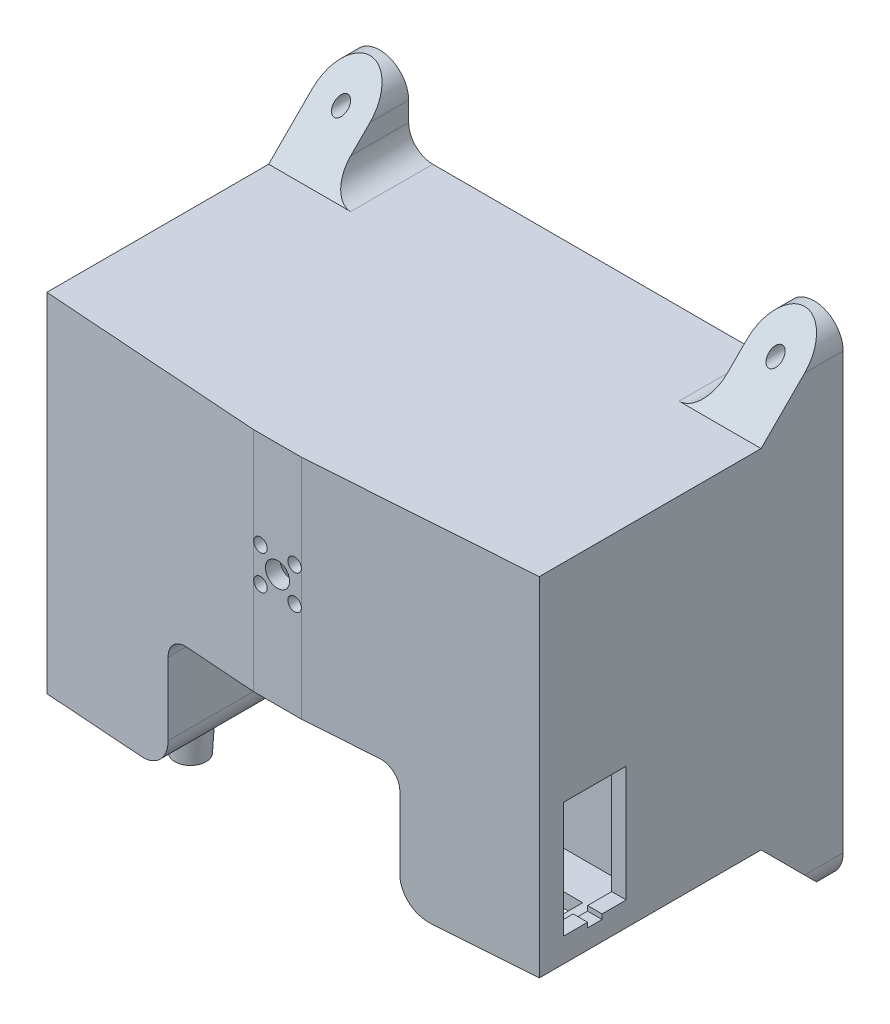
SolidWorks part; units mm, degrees
material "ABS"
ref_plane "Спереди" through (0, 0, 0) normal (0, 0, 1) x (1, 0, 0)
ref_plane "Сверху" through (0, 0, 0) normal (0, 1, 0) x (1, 0, 0)
ref_plane "Справа" through (0, 0, 0) normal (1, 0, 0) x (0, 0, -1)
sketch "Model" plane through (0, 0, 0) normal (0, 0, 1) x (1, 0, 0)
  line L0 (-25, 35) -> (-25, 20)
  line L1 (-70, 40) -> (-30, 40)
  line L2 (-75, 20) -> (-75, 35)
  line L3 (1, 49) -> (1, 95)
  line L5 (0, 95) -> (0, 78.8869)
  line L6 (-10, 85) -> (-10, 95)
  line L7 (-90, 85) -> (-10, 85)
  line L8 (-90, 95) -> (-90, 85)
  line L9 (-100, 78.8869) -> (-100, 95)
  line L10 (-100, 78.8869) -> (-100, 76.8869)
  line L11 (0, 76.8869) -> (0, 65)
  line L12 (-100, 65) -> (-100, 63)
  line L13 (-100, 65) -> (-100, 76.8869)
  line L14 (-90, 15) -> (-90, 5)
  line L15 (-80, 15) -> (-90, 15)
  line L16 (-75, 35) -> (-75, 20)
  line L17 (-30, 40) -> (-70, 40)
  line L18 (-25, 20) -> (-25, 35)
  line L19 (-10, 15) -> (-20, 15)
  line L20 (-10, 5) -> (-10, 15)
  line L21 (0, 28) -> (0, 5)
  line L22 (-10, 28) -> (0, 28)
  line L23 (-12, 48) -> (-12, 30)
  line L24 (0, 50) -> (-10, 50)
  line L25 (0, 63) -> (0, 50)
  line L26 (0, 78.8869) -> (0, 76.8869)
  line L27 (-100, 5) -> (-100, 63)
  line L28 (-101, 95) -> (-101, 5)
  line L29 (-89, 86) -> (-89, 95)
  line L30 (-11, 86) -> (-89, 86)
  line L31 (-11, 95) -> (-11, 86)
  line L32 (-10, 49) -> (1, 49)
  line L33 (-11, 30) -> (-11, 48)
  line L34 (1, 29) -> (-10, 29)
  line L35 (1, 5) -> (1, 29)
  line L36 (-11, 14) -> (-11, 5)
  line L37 (-20, 14) -> (-11, 14)
  line L38 (-26, 35) -> (-26, 20)
  line L39 (-70, 39) -> (-30, 39)
  line L40 (-74, 20) -> (-74, 35)
  line L41 (0, 65) -> (0, 63)
  line L42 (-89, 5) -> (-89, 14)
  line L52 (-80, 14) -> (-89, 14)
  arc A0 (-25, 35) -> (-30, 40) centre (-30, 35) ccw
  arc A1 (-70, 40) -> (-75, 35) centre (-70, 35) ccw
  circle A2 centre (-95, 95) radius 1.4
  circle A3 centre (-95, 95) radius 2.4
  circle A4 centre (-5, 95) radius 1.4
  circle A5 centre (-5, 95) radius 2.4
  circle A6 centre (-95, 5) radius 1.4
  circle A7 centre (-95, 5) radius 2.4
  circle A8 centre (-5, 5) radius 2.4
  circle A9 centre (-5, 5) radius 1.4
  arc A10 (0, 95) -> (-10, 95) centre (-5, 95) ccw
  arc A11 (-90, 95) -> (-100, 95) centre (-95, 95) ccw
  arc A12 (-100, 5) -> (-90, 5) centre (-95, 5) ccw
  arc A13 (-80, 15) -> (-75, 20) centre (-80, 20) ccw
  arc A14 (-70, 40) -> (-75, 35) centre (-70, 35) ccw
  arc A15 (-25, 35) -> (-30, 40) centre (-30, 35) ccw
  arc A16 (-25, 20) -> (-20, 15) centre (-20, 20) ccw
  arc A17 (-10, 5) -> (0, 5) centre (-5, 5) ccw
  arc A18 (-12, 30) -> (-10, 28) centre (-10, 30) ccw
  arc A19 (-10, 50) -> (-12, 48) centre (-10, 48) ccw
  arc A20 (-89, 95) -> (-101, 95) centre (-95, 95) ccw
  arc A21 (1, 95) -> (-11, 95) centre (-5, 95) ccw
  arc A22 (-10, 49) -> (-11, 48) centre (-10, 48) ccw
  arc A23 (-11, 30) -> (-10, 29) centre (-10, 30) ccw
  arc A24 (-11, 5) -> (1, 5) centre (-5, 5) ccw
  arc A25 (-26, 20) -> (-20, 14) centre (-20, 20) ccw
  arc A26 (-26, 35) -> (-30, 39) centre (-30, 35) ccw
  arc A27 (-70, 39) -> (-74, 35) centre (-70, 35) ccw
  arc A28 (-80, 14) -> (-74, 20) centre (-80, 20) ccw
  arc A29 (-101, 5) -> (-89, 5) centre (-95, 5) ccw
extrude "Бобышка-Вытянуть1" add sketch "Model" along normal blind 60 contours L28 A29 L42 L52 A28 L40 A27 L39 A26 L38 A25 L37 L36 A24 L35 L34 A23 L33 A22 L32 L3 A21 L31 L30 L29 A20 L24 A19 L23 A18 L22 L21 A17 L20 L19 A16 L0 A0 L1 A1 L2 A13 L15 L14 A12 L27 L12 L13 L10 L9 region at (-4.5, 49.1442, 0)
sketch "Эскиз2" plane through (0, 0, 60) normal (0, 0, 1) x (1, 0, 0)
  line L0 (-90, 85) -> (-100, 85)
  line L1 (-100, 5) -> (-100, 95) construction
  line L2 (-100, 85) -> (-100, 95)
  line L3 (-90, 95) -> (-90, 85)
  line L4 (-10, 95) -> (-10, 85)
  line L5 (-10, 85) -> (0, 85)
  line L6 (0, 95) -> (0, 50) construction
  line L7 (0, 85) -> (0, 95)
  line L8 (-10, 5) -> (-10, 15)
  line L9 (-10, 15) -> (0, 15)
  line L10 (0, 28) -> (0, 5) construction
  line L11 (0, 15) -> (0, 5)
  line L12 (-90, 5) -> (-90, 15)
  line L13 (-90, 15) -> (-100, 15)
  line L14 (-100, 15) -> (-100, 5)
  arc A0 (-90, 95) -> (-100, 95) centre (-95, 95) ccw construction
  arc A1 (-90, 95) -> (-100, 95) centre (-95, 95) ccw
  arc A2 (0, 95) -> (-10, 95) centre (-5, 95) ccw construction
  arc A3 (0, 95) -> (-10, 95) centre (-5, 95) ccw
  arc A4 (-10, 5) -> (0, 5) centre (-5, 5) ccw construction
  arc A5 (-10, 5) -> (0, 5) centre (-5, 5) ccw
  arc A6 (-100, 5) -> (-90, 5) centre (-95, 5) ccw construction
  arc A7 (-100, 5) -> (-90, 5) centre (-95, 5) ccw
extrude "Бобышка-Вытянуть2" add sketch "Эскиз2" against normal up to surface (60 mm away) up to face at (-40.1857, 40.5385, 0)
ref_plane "Плоскость1" through (0, 62.5, 0) normal (0, 1, 0) x (1, 0, 0)
sketch "Эскиз4" plane through (0, 62.5, 0) normal (0, 1, 0) x (1, 0, 0)
  line L0 (-100, -60) -> (-55, -63.1467)
  line L1 (-55, -63.1467) -> (-45, -63.1467)
  line L2 (-50, 0) -> (-50, -60) construction
  line L3 (-70, 0) -> (-30, 0) construction
  line L4 (-70, -60) -> (-30, -60) construction
  line L5 (-50, -60) -> (-50, -63.1467) construction
  line L6 (-100, -60) -> (-101, -60)
  line L7 (-101, -60) -> (-101, -62.9374)
  line L8 (-101, -62.9374) -> (-55, -66.154)
  line L9 (-55, -66.154) -> (-45, -66.154)
  line L10 (-55, -63.1467) -> (-55, -66.154) construction
  line L11 (1, -62.9374) -> (-45, -66.154)
  line L12 (0, -60) -> (-45, -63.1467)
  line L13 (1, -60) -> (1, -62.9374)
  line L14 (0, -60) -> (1, -60)
  point P16 (-50, -66.154)
  dimension "D1" = 4
  dimension "D2" = 5
  dimension "D3" = 3
extrude "Бобышка-Вытянуть3" add sketch "Эскиз4" along normal up to surface (22.5 mm away) up to face at (-50, 85, 30)
extrude "Бобышка-Вытянуть4" add sketch "Эскиз4<2>" against normal up to surface (48.5 mm away) up to face at (-15.5, 14, 30)
sketch "Эскиз4<2>" plane through (0, 62.5, 0) normal (0, 1, 0) x (1, 0, 0) same geometry as "Эскиз4"
sketch "Эскиз5" plane through (0, 0, 0) normal (0, 0, -1) x (-1, 0, 0)
  line L0 (-1, 29) -> (10, 29) construction
  line L1 (11, 30) -> (11, 48) construction
  line L2 (10, 49) -> (-1, 49) construction
  line L3 (74, 20) -> (74, 35) construction
  line L4 (70, 39) -> (30, 39) construction
  line L5 (26, 35) -> (26, 20) construction
  line L6 (-1, 29) -> (10, 29)
  line L7 (11, 30) -> (11, 48)
  line L8 (10, 49) -> (-1, 49)
  line L9 (74, 20) -> (74, 35)
  line L10 (70, 39) -> (30, 39)
  line L11 (26, 35) -> (26, 20)
  line L12 (-1, 49) -> (-1, 29)
  line L13 (20, 14) -> (80, 14)
  arc A0 (10, 29) -> (11, 30) centre (10, 30) ccw construction
  arc A1 (11, 48) -> (10, 49) centre (10, 48) ccw construction
  arc A2 (74, 20) -> (80, 14) centre (80, 20) ccw construction
  arc A3 (74, 35) -> (70, 39) centre (70, 35) ccw construction
  arc A4 (30, 39) -> (26, 35) centre (30, 35) ccw construction
  arc A5 (20, 14) -> (26, 20) centre (20, 20) ccw construction
  arc A6 (10, 29) -> (11, 30) centre (10, 30) ccw
  arc A7 (11, 48) -> (10, 49) centre (10, 48) ccw
  arc A8 (74, 20) -> (80, 14) centre (80, 20) ccw
  arc A9 (74, 35) -> (70, 39) centre (70, 35) ccw
  arc A10 (30, 39) -> (26, 35) centre (30, 35) ccw
  arc A11 (20, 14) -> (26, 20) centre (20, 20) ccw
extrude "Вырез-Вытянуть1" cut sketch "Эскиз5" against normal through all
sketch "Эскиз6" plane through (0, 0, 60) normal (0, 0, 1) x (1, 0, 0)
  line L8 (0, 49) -> (0, 50)
  line L9 (0, 50) -> (-10, 50)
  line L10 (-12, 48) -> (-12, 30)
  line L11 (-10, 28) -> (0, 28)
  line L12 (0, 28) -> (0, 29)
  line L13 (0, 29) -> (-10, 29)
  line L14 (-11, 30) -> (-11, 48)
  line L15 (-10, 49) -> (0, 49)
  line L16 (0, 49) -> (0, 50)
  line L17 (0, 50) -> (-10, 50)
  line L18 (0, 14) -> (0, 15)
  line L19 (0, 15) -> (-20, 15)
  line L20 (-25, 20) -> (-25, 35)
  line L21 (-30, 40) -> (-70, 40)
  line L22 (-75, 35) -> (-75, 20)
  line L23 (-80, 15) -> (-100, 15)
  line L24 (-100, 15) -> (-100, 14)
  line L25 (-100, 14) -> (-101, 14)
  line L26 (-101, 14) -> (-101, 5)
  line L27 (-89, 5) -> (-89, 14)
  line L28 (-89, 14) -> (-80, 14)
  line L29 (-74, 20) -> (-74, 35)
  line L30 (-70, 39) -> (-30, 39)
  line L31 (-26, 35) -> (-26, 20)
  line L32 (-20, 14) -> (-11, 14)
  line L33 (-11, 14) -> (-11, 5)
  line L34 (1, 5) -> (1, 14)
  line L35 (1, 14) -> (0, 14)
  line L36 (0, 14) -> (0, 15)
  line L37 (0, 15) -> (-20, 15)
  line L38 (-25, 20) -> (-25, 35)
  line L39 (-30, 40) -> (-70, 40)
  line L40 (-75, 35) -> (-75, 20)
  line L41 (-80, 15) -> (-100, 15)
  line L42 (-100, 15) -> (-100, 14)
  line L43 (-100, 14) -> (-101, 14)
  line L44 (-101, 14) -> (-101, 5)
  line L45 (-89, 5) -> (-89, 14)
  line L46 (-89, 14) -> (-80, 14)
  line L47 (-74, 20) -> (-74, 35)
  line L48 (-70, 39) -> (-30, 39)
  line L49 (-26, 35) -> (-26, 20)
  line L50 (-20, 14) -> (-11, 14)
  line L51 (-11, 14) -> (-11, 5)
  line L52 (1, 5) -> (1, 14)
  line L53 (1, 14) -> (0, 14)
  line L54 (-12, 48) -> (-12, 30)
  line L55 (-10, 28) -> (0, 28)
  line L56 (0, 28) -> (0, 29)
  line L57 (0, 29) -> (-10, 29)
  line L58 (-11, 30) -> (-11, 48)
  line L59 (-10, 49) -> (0, 49)
  arc A4 (-10, 50) -> (-12, 48) centre (-10, 48) ccw
  arc A5 (-12, 30) -> (-10, 28) centre (-10, 30) ccw
  arc A6 (-11, 30) -> (-10, 29) centre (-10, 30) ccw
  arc A7 (-10, 49) -> (-11, 48) centre (-10, 48) ccw
  arc A8 (-10, 50) -> (-12, 48) centre (-10, 48) ccw
  arc A9 (-12, 30) -> (-10, 28) centre (-10, 30) ccw
  arc A10 (-25, 20) -> (-20, 15) centre (-20, 20) ccw
  arc A11 (-25, 35) -> (-30, 40) centre (-30, 35) ccw
  arc A12 (-70, 40) -> (-75, 35) centre (-70, 35) ccw
  arc A13 (-80, 15) -> (-75, 20) centre (-80, 20) ccw
  arc A14 (-101, 5) -> (-89, 5) centre (-95, 5) ccw
  arc A15 (-80, 14) -> (-74, 20) centre (-80, 20) ccw
  arc A16 (-70, 39) -> (-74, 35) centre (-70, 35) ccw
  arc A17 (-26, 35) -> (-30, 39) centre (-30, 35) ccw
  arc A18 (-26, 20) -> (-20, 14) centre (-20, 20) ccw
  arc A19 (-11, 5) -> (1, 5) centre (-5, 5) ccw
  arc A20 (-25, 20) -> (-20, 15) centre (-20, 20) ccw
  arc A21 (-25, 35) -> (-30, 40) centre (-30, 35) ccw
  arc A22 (-70, 40) -> (-75, 35) centre (-70, 35) ccw
  arc A23 (-80, 15) -> (-75, 20) centre (-80, 20) ccw
  arc A24 (-101, 5) -> (-89, 5) centre (-95, 5) ccw
  arc A25 (-80, 14) -> (-74, 20) centre (-80, 20) ccw
  arc A26 (-70, 39) -> (-74, 35) centre (-70, 35) ccw
  arc A27 (-26, 35) -> (-30, 39) centre (-30, 35) ccw
  arc A28 (-26, 20) -> (-20, 14) centre (-20, 20) ccw
  arc A29 (-11, 5) -> (1, 5) centre (-5, 5) ccw
  arc A30 (-11, 30) -> (-10, 29) centre (-10, 30) ccw
  arc A31 (-10, 49) -> (-11, 48) centre (-10, 48) ccw
  dimension "D1" = 0
  dimension "D2" = 0
extrude "Бобышка-Вытянуть5" add sketch "Эскиз6" along normal blind 3
sketch "Эскиз7" plane through (0, 39, 0) normal (0, -1, 0) x (1, 0, 0)
  line L0 (-70, 65.1051) -> (-55, 66.154)
  line L1 (-55, 66.154) -> (-45, 66.154)
  line L2 (-45, 66.154) -> (-30, 65.1051)
  line L3 (-30, 65.1051) -> (-30, 61.1051)
  line L4 (-30, 65.1051) -> (-30, 0) construction
  line L5 (-30, 61.1051) -> (-70, 61.1051)
  line L6 (-70, 65.1051) -> (-70, 0) construction
  line L7 (-70, 61.1051) -> (-70, 65.1051)
  dimension "D1" = 4
extrude "Бобышка-Вытянуть6" add sketch "Эскиз7" against normal blind 1
sketch "Эскиз8" plane through (0, 0, 0) normal (0, 0, -1) x (-1, 0, 0)
  line L0 (45, 40) -> (30, 40) construction
  line L1 (0, 85) -> (45, 85) construction
  line L2 (0, 85) -> (0, 50) construction
  line L3 (45, 85) -> (55, 85) construction
  line L4 (55, 85) -> (100, 85) construction
  line L5 (100, 15) -> (100, 85) construction
  line L6 (100, 15) -> (80, 15) construction
  line L7 (75, 20) -> (75, 35) construction
  line L8 (70, 40) -> (55, 40) construction
  line L9 (45, 40) -> (55, 40) construction
  line L10 (25, 35) -> (25, 20) construction
  line L11 (20, 15) -> (0, 15) construction
  line L12 (0, 28) -> (0, 15) construction
  line L14 (12, 30) -> (12, 48) construction
  line L15 (10, 50) -> (0, 50) construction
  line L16 (10, 28) -> (0, 28) construction
  line L17 (10, 28) -> (0, 28)
  line L18 (10, 50) -> (0, 50)
  line L19 (12, 30) -> (12, 48)
  line L20 (0, 28) -> (0, 15)
  line L21 (20, 15) -> (0, 15)
  line L22 (25, 35) -> (25, 20)
  line L23 (45, 40) -> (30, 40)
  line L24 (45, 40) -> (55, 40)
  line L25 (70, 40) -> (55, 40)
  line L26 (75, 20) -> (75, 35)
  line L27 (100, 15) -> (80, 15)
  line L28 (100, 15) -> (100, 85)
  line L29 (55, 85) -> (100, 85)
  line L30 (45, 85) -> (55, 85)
  line L31 (0, 85) -> (0, 50)
  line L32 (0, 85) -> (45, 85)
  line L33 (10, 26) -> (2, 26)
  line L34 (2, 26) -> (2, 17)
  line L35 (20, 17) -> (2, 17)
  line L36 (23, 35) -> (23, 20)
  line L37 (45, 42) -> (30, 42)
  line L38 (45, 42) -> (55, 42)
  line L39 (70, 42) -> (55, 42)
  line L40 (77, 20) -> (77, 35)
  line L41 (98, 17) -> (80, 17)
  line L42 (98, 17) -> (98, 83)
  line L43 (55, 83) -> (98, 83)
  line L44 (45, 83) -> (55, 83)
  line L45 (2, 83) -> (45, 83)
  line L46 (2, 83) -> (2, 52)
  line L47 (10, 52) -> (2, 52)
  line L48 (14, 30) -> (14, 48)
  arc A0 (75, 20) -> (80, 15) centre (80, 20) ccw construction
  arc A1 (75, 35) -> (70, 40) centre (70, 35) ccw construction
  arc A2 (30, 40) -> (25, 35) centre (30, 35) ccw construction
  arc A3 (20, 15) -> (25, 20) centre (20, 20) ccw construction
  arc A4 (10, 28) -> (12, 30) centre (10, 30) ccw construction
  arc A5 (12, 48) -> (10, 50) centre (10, 48) ccw construction
  arc A6 (12, 48) -> (10, 50) centre (10, 48) ccw
  arc A7 (10, 28) -> (12, 30) centre (10, 30) ccw
  arc A8 (20, 15) -> (25, 20) centre (20, 20) ccw
  arc A9 (30, 40) -> (25, 35) centre (30, 35) ccw
  arc A10 (75, 35) -> (70, 40) centre (70, 35) ccw
  arc A11 (75, 20) -> (80, 15) centre (80, 20) ccw
  arc A12 (20, 17) -> (23, 20) centre (20, 20) ccw
  arc A13 (30, 42) -> (23, 35) centre (30, 35) ccw
  arc A14 (77, 35) -> (70, 42) centre (70, 35) ccw
  arc A15 (77, 20) -> (80, 17) centre (80, 20) ccw
  arc A16 (14, 48) -> (10, 52) centre (10, 48) ccw
  arc A17 (10, 26) -> (14, 30) centre (10, 30) ccw
  dimension "D1" = 2
extrude "Бобышка-Вытянуть7" add sketch "Эскиз8" against normal blind 62
sketch "Эскиз10" plane through (0, 86, 0) normal (0, 1, 0) x (1, 0, 0)
  line L6 (1, -62.9374) -> (1, -60)
  line L7 (1, -60) -> (-101, -60)
  line L8 (-101, -60) -> (-101, -62.9374)
  line L9 (-101, -62.9374) -> (-55, -66.154)
  line L10 (-55, -66.154) -> (-45, -66.154)
  line L11 (-45, -66.154) -> (1, -62.9374)
  line L12 (1, -62.9374) -> (1, -60)
  line L13 (1, -60) -> (-101, -60)
  line L14 (-101, -60) -> (-101, -62.9374)
  line L15 (-101, -62.9374) -> (-55, -66.154)
  line L16 (-55, -66.154) -> (-45, -66.154)
  line L17 (-45, -66.154) -> (1, -62.9374)
  dimension "D1" = 0
extrude "Бобышка-Вытянуть8" add sketch "Эскиз10" against normal up to surface (3 mm away) up to face at (-50, 83, 40.7133)
sketch "Эскиз11" plane through (-11, 0, 0) normal (-1, 0, 0) x (0, 0, 1)
  line L0 (0, 101) -> (2, 101) construction
  line L1 (60, 101) -> (0, 101) construction
  line L2 (2, 101) -> (17, 86)
  line L3 (60, 86) -> (0, 86) construction
  line L4 (17, 86) -> (60, 86)
  line L5 (60, 86) -> (60, 101) construction
  line L6 (60, 101) -> (2, 101)
  line L7 (0, 101) -> (0, 95) construction
  line L8 (31.5, -1) -> (31.5, 101) construction
  line L9 (0, -1) -> (63, -1) construction
  line L10 (31.5, 50) -> (20, 50) construction
  line L15 (60, -1) -> (2, -1)
  line L16 (60, 86) -> (75, 86)
  line L17 (60, 86) -> (60, 101) construction
  line L18 (60, 101) -> (75, 101)
  line L19 (75, 86) -> (75, 101)
  line L20 (60, -1) -> (75, -1)
  line L21 (75, 14) -> (75, -1)
  line L22 (60, 14) -> (75, 14)
  line L23 (17, 14) -> (60, 14)
  line L24 (2, -1) -> (17, 14)
  dimension "D1" = 2
  dimension "D2" = 45
  dimension "D3" = 15
extrude "Вырез-Вытянуть2" cut sketch "Эскиз11" against normal through all both and the other way through all
sketch "Эскиз13" plane through (0, 0, 0) normal (0, 0, -1) x (-1, 0, 0)
  line L0 (-1, 5) -> (-1, 29) construction
  line L1 (2, 52) -> (-1, 52)
  line L2 (2, 52) -> (2, 26)
  line L3 (2, 26) -> (-1, 26)
  line L4 (-1, 52) -> (-1, 26)
  line L5 (2, 26) -> (10, 26) construction
extrude "Бобышка-Вытянуть9" add sketch "Эскиз13" against normal up to surface (63.1472 mm away) up to face at (-16.4877, 40.4704, 64.1603)
sketch "Эскиз14" plane through (0, 0, 0) normal (0, 0, -1) x (-1, 0, 0)
  line L0 (2, 26) -> (10, 26) construction
  line L1 (2, 52) -> (14, 52)
  line L2 (2, 52) -> (2, 26)
  line L3 (2, 26) -> (14, 26)
  line L4 (14, 52) -> (14, 26)
  line L5 (14, 30) -> (14, 48) construction
extrude "Вырез-Вытянуть3" cut sketch "Эскиз14" against normal through all both
sketch "Эскиз15" plane through (0, 52, 0) normal (0, -1, 0) x (1, 0, 0)
  line L4 (-2, 60.1399) -> (-2, 63.1472)
  line L5 (-2, 63.1472) -> (-14, 63.9863)
  line L6 (-14, 63.9863) -> (-14, 60.979)
  line L7 (-14, 60.979) -> (-2, 60.1399)
  line L8 (-2, 60.1399) -> (-2, 63.1472)
  line L9 (-2, 63.1472) -> (-14, 63.9863)
  line L10 (-14, 63.9863) -> (-14, 60.979)
  line L11 (-14, 60.979) -> (-2, 60.1399)
  dimension "D1" = 0
extrude "Бобышка-Вытянуть10" add sketch "Эскиз15" along normal up to surface (26 mm away) up to face at (-8, 26, 62.0631)
sketch "Эскиз16" plane through (1, 0, 0) normal (1, 0, 0) x (0, 0, -1)
  line L0 (-62.9374, 86) -> (-62.9374, 14) construction
  line L1 (-44.9374, 19) -> (-49.9374, 19)
  line L2 (-44.9374, 19) -> (-44.9374, 43)
  line L3 (-44.9374, 43) -> (-57.9374, 43)
  line L4 (-57.9374, 19) -> (-57.9374, 43)
  line L5 (-62.9374, 14) -> (-17, 14) construction
  line L6 (-51.4374, 19) -> (-51.4374, 18.5) construction
  line L7 (-52.9374, 19) -> (-51.4374, 19) construction
  line L8 (-52.9374, 18) -> (-49.9374, 18)
  line L9 (-52.9374, 18) -> (-52.9374, 19)
  line L10 (-51.4374, 19) -> (-49.9374, 19) construction
  line L11 (-49.9374, 18) -> (-49.9374, 19)
  line L12 (-52.9374, 18) -> (-49.9374, 19) construction
  line L13 (-52.9374, 19) -> (-49.9374, 18) construction
  line L14 (-51.4374, 19) -> (-52.9374, 19) construction
  line L15 (-52.9374, 19) -> (-57.9374, 19)
  line L16 (-49.9374, 19) -> (-51.4374, 19) construction
  line L17 (-51.4374, 43) -> (-51.4374, 19) construction
  dimension "D1" = 24
  dimension "D2" = 13
  dimension "D3" = 5
  dimension "D4" = 5
  dimension "D5" = 1
  dimension "D6" = 3
extrude "Вырез-Вытянуть4" cut sketch "Эскиз16" against normal blind 5
ref_plane "Плоскость2" through (0, 0, 60.1399) normal (0, 0, -1) x (-1, 0, 0)
sketch "Эскиз17" plane through (0, 0, 60.1399) normal (0, 0, -1) x (-1, 0, 0)
  line L0 (2, 52) -> (26, 52)
  line L1 (2, 83) -> (2, 17) construction
  line L3 (2, 17) -> (20, 17) construction
  line L4 (23, 20) -> (23, 35) construction
  line L5 (2, 17) -> (20, 17) construction
  line L6 (23, 20) -> (23, 35) construction
  line L7 (2, 52) -> (2, 49) construction
  line L8 (2, 49) -> (23, 49)
  line L9 (23, 49) -> (23, 35)
  line L10 (26, 52) -> (26, 40.7446)
  line L11 (2, 49) -> (2, 17) construction
  line L12 (2, 49) -> (2, 52)
  arc A0 (20, 17) -> (23, 20) centre (20, 20) ccw construction
  arc A1 (20, 17) -> (23, 20) centre (20, 20) ccw construction
  arc A2 (30, 42) -> (23, 35) centre (30, 35) ccw construction
  arc A3 (26, 40.7446) -> (23, 35) centre (30, 35) ccw
  arc A4 (30, 42) -> (26, 40.7446) centre (30, 35) ccw construction
  dimension "D1" = 35
  dimension "D2" = 3
  dimension "D3" = 3
extrude "Бобышка-Вытянуть11" add sketch "Эскиз17" against normal up to surface up to face at (-24.6594, 41.7086, 61.7244)
extrude "Бобышка-Вытянуть12" add sketch "Эскиз17<2>" along normal blind 20
sketch "Эскиз17<2>" plane through (0, 0, 60.1399) normal (0, 0, -1) x (-1, 0, 0) same geometry as "Эскиз17"
sketch "Эскиз18" plane through (0, 0, 40.1399) normal (0, 0, -1) x (-1, 0, 0)
  line L0 (2, 83) -> (2, 17) construction
  line L1 (20, 17) -> (2, 17) construction
  line L2 (23, 49) -> (23, 20) construction
  line L3 (26, 40.7446) -> (26, 52) construction
  line L4 (2, 83) -> (2, 17) construction
  line L5 (20, 17) -> (2, 17)
  line L6 (23, 49) -> (23, 20)
  line L7 (26, 40.7446) -> (26, 52)
  line L8 (26, 52) -> (2, 52) construction
  line L9 (2, 49) -> (23, 49) construction
  line L10 (26, 52) -> (2, 52)
  line L11 (2, 49) -> (23, 49)
  line L12 (2, 49) -> (2, 52)
  line L13 (2, 17) -> (2, 49)
  arc A0 (20, 17) -> (23, 20) centre (20, 20) ccw construction
  arc A1 (26, 40.7446) -> (23, 35) centre (30, 35) ccw construction
  arc A2 (20, 17) -> (23, 20) centre (20, 20) ccw
  arc A3 (26, 40.7446) -> (23, 35) centre (30, 35) ccw
  line M6 (2, 52) -> (2, 49)
  line M7 (2, 49) -> (23, 49)
  line M8 (23, 49) -> (23, 35)
  arc M9 (23, 35) -> (26, 40.7446) centre (30, 35) cw
  line M10 (26, 40.7446) -> (26, 52)
  line M11 (26, 52) -> (2, 52)
extrude "Бобышка-Вытянуть13" add sketch "Эскиз18" along normal blind 3 contours L5 A2 L6 L13 M8 M7 | M11 M6 M7 M8 M9 M10 region at (-12.4717, 33.0442, 40.1399) region at (-2.2941, 50.5, 40.1399)
sketch "Эскиз19" plane through (0, 14, 0) normal (0, -1, 0) x (1, 0, 0)
  line L1 (-15, 47.9374) -> (-5, 47.9374)
  line L2 (-15, 47.9374) -> (-15, 57.9374)
  line L3 (-15, 57.9374) -> (-5, 57.9374)
  line L4 (-5, 47.9374) -> (-5, 57.9374)
  line L5 (-15, 47.9374) -> (-5, 57.9374) construction
  line L6 (-15, 57.9374) -> (-5, 47.9374) construction
  line L7 (1, 62.9374) -> (1, 17) construction
  point P0 (-10, 52.9374)
  dimension "D1" = 5
  dimension "D2" = 10
  dimension "D3" = 10
  dimension "D4" = 6
extrude "Вырез-Вытянуть5" cut sketch "Эскиз19" against normal blind 3
fillet "Скругление1" radius 10 3 edges at (-26, 52, 49.479) (-26, 46.3723, 61.8181) (-14, 52, 60.979)
fillet "Скругление2" radius 5 4 edges at (-98, 17, 30.0699) (-98, 83, 30.0699) (-2, 83, 30.0699) (-2, 17, 18.5699)
fillet "Скругление3" radius 5 4 edges at (-11, 86, 8.5) (-89, 86, 8.5) (-89, 14, 8.5) (-11, 14, 8.5)
fillet "Скругление4" radius 5 3 edges at (-26, 41.3723, 37.1399) (-23.0711, 49.0711, 37.1399) (-9, 52, 37.1399)
fillet "Скругление5" radius 5 1 edges at (-23, 49, 50.8741)
sketch "Эскиз21" plane through (0, 0, 66.154) normal (0, 0, 1) x (1, 0, 0)
  line L0 (-50, 86) -> (-50, 39) construction
  line L1 (-55, 86) -> (-45, 86) construction
  line L2 (-55, 39) -> (-45, 39) construction
  line L3 (-50, 62.5) -> (-53.5355, 66.0355) construction
  circle A0 centre (-50, 62.5) radius 2.5
  circle A1 centre (-50, 62.5) radius 5 construction
  circle A2 centre (-53.5355, 66.0355) radius 1.4
  circle A3 centre (-46.4645, 66.0355) radius 1.4
  circle A4 centre (-46.4645, 58.9645) radius 1.4
  circle A5 centre (-53.5355, 58.9645) radius 1.4
  point P19 (-50, 62.5)
  dimension "D1" = 5
  dimension "D2" = 45
  dimension "D3" = 10
  dimension "D4" = 2.8
  dimension "D5" = 4
extrude "Вырез-Вытянуть6" cut sketch "Эскиз21" against normal through all
sketch "Эскиз22" plane through (0, 0, 0) normal (0, 0, -1) x (-1, 0, 0)
  line L0 (5, 101) -> (5, 95) construction
  line L1 (50, 86) -> (50, 98.3125) construction
  line L2 (16, 86) -> (84, 86) construction
  line L3 (95, -1) -> (95, 101) construction
  line L4 (95, 50) -> (-1, 50) construction
  line L5 (-1, 5) -> (-1, 95) construction
  arc A0 (11, 95) -> (-1, 95) centre (5, 95) ccw construction
  circle A1 centre (5, 95) radius 1.4
  circle A2 centre (95, 95) radius 1.4
  arc A3 (89, 5) -> (101, 5) centre (95, 5) ccw construction
  arc A4 (101, 95) -> (89, 95) centre (95, 95) ccw construction
  circle A5 centre (95, 5) radius 1.4
  circle A6 centre (5, 5) radius 1.4
  dimension "D1" = 2.8
extrude "Вырез-Вытянуть7" cut sketch "Эскиз22" against normal through all
sketch "Эскиз20" plane through (0, 14, 0) normal (0, -1, 0) x (1, 0, 0)
  line L0 (-101, 43.6716) -> (-80, 43.6716) construction
  line L1 (-101, 62.9374) -> (-101, 17) construction
  line L2 (-80, 64.4059) -> (-80, 0) construction
  line L3 (-90.5, 43.6716) -> (-90.5, 63.6716) construction
  line L4 (-80, 64.4059) -> (-101, 62.9374) construction
  circle A0 centre (-90.5, 43.6716) radius 4
  dimension "D1" = 20
  dimension "D2" = 8
extrude "Бобышка-Вытянуть14" add sketch "Эскиз20" along normal blind 15 draft 3
fillet "Скругление6" radius 5 1 edges at (-86.5, 14, 43.6716)
sketch "Эскиз23" plane through (0, -1, 0) normal (0, -1, 0) x (1, 0, 0)
  circle A0 centre (-90.5, 43.6716) radius 2.0139
  circle A1 centre (-90.5, 43.6716) radius 3.2139 construction
  dimension "D1" = 1.2
extrude "Вырез-Вытянуть8" cut sketch "Эскиз23" against normal blind 27
sketch "Эскиз24" plane through (0, 0, 0) normal (0, 0, -1) x (-1, 0, 0)
  line L0 (7, 83) -> (45, 83) construction
  line L1 (37, 83) -> (40, 83)
  line L2 (37, 83) -> (37, 42)
  line L3 (37, 42) -> (40, 42)
  line L4 (40, 83) -> (40, 42)
  line L5 (30, 42) -> (70, 42) construction
  line L6 (2, 78) -> (2, 22) construction
  line L7 (50, 42) -> (50, 83) construction
  line L8 (93, 83) -> (7, 83) construction
  line L9 (63, 42) -> (60, 42)
  line L10 (60, 83) -> (60, 42)
  line L11 (63, 83) -> (60, 83)
  line L12 (63, 83) -> (63, 42)
  dimension "D1" = 3
  dimension "D2" = 35
extrude "Бобышка-Вытянуть15" add sketch "Эскиз24" against normal offset from surface (60.7922 mm away) 2 up to face at (-23.7517, 61.8972, 61.6609)
sketch "Эскиз25" plane through (-37, 0, 0) normal (1, 0, 0) x (0, 0, -1)
  line L0 (-60.5824, 83) -> (-60.5824, 42) construction
  line L1 (-60.5824, 83) -> (0, 83) construction
  circle A0 centre (-45.5824, 73) radius 7.5
  dimension "D3" = 15
  dimension "D1" = 15
  dimension "D2" = 10
extrude "Вырез-Вытянуть9" cut sketch "Эскиз25" against normal blind 3 contours A0
sketch "Эскиз26" plane through (-60, 0, 0) normal (1, 0, 0) x (0, 0, -1)
  line L0 (0, 62.5) -> (-60.5824, 62.5) construction
  line L1 (0, 83) -> (0, 42) construction
  line L2 (-60.5824, 83) -> (-60.5824, 42) construction
  circle A0 centre (-45.5824, 73) radius 7.5 construction
  circle A1 centre (-45.5824, 73) radius 7.5 construction
  circle A2 centre (-45.5824, 52) radius 7.5
extrude "Вырез-Вытянуть10" cut sketch "Эскиз26" against normal blind 3
